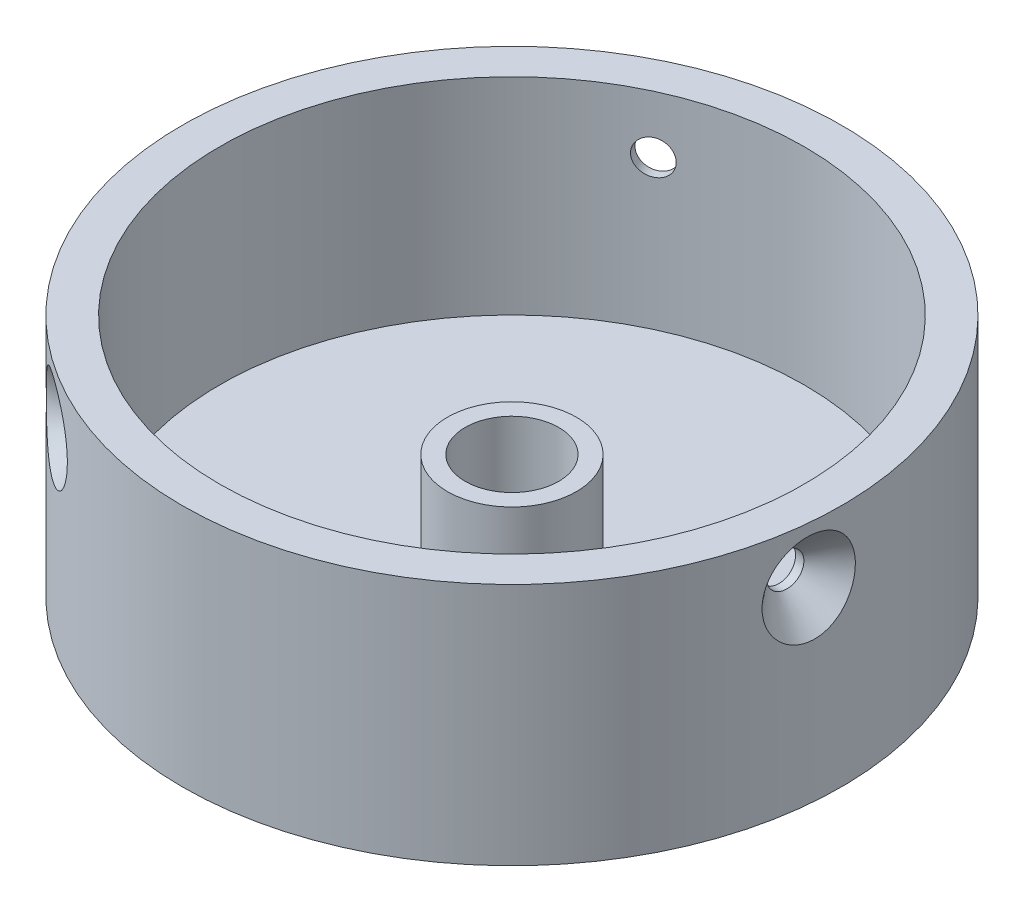
SolidWorks part; units mm, degrees
ref_plane "Front Plane" through (0, 0, 0) normal (0, 0, 1) x (1, 0, 0)
ref_plane "Top Plane" through (0, 0, 0) normal (0, 1, 0) x (1, 0, 0)
ref_plane "Right Plane" through (0, 0, 0) normal (1, 0, 0) x (0, 0, -1)
sketch "Sketch1" plane through (0, 0, 0) normal (0, 1, 0) x (1, 0, 0)
  circle A0 centre (0, 0) radius 23
  dimension "D1" = 46
extrude "Boss-Extrude1" add sketch "Sketch1" along normal blind 17
shell "Shell1" thickness 2.6 removed face at (0, 17, 23)
sketch "Sketch2" plane through (0, 0, 0) normal (0, -1, 0) x (1, 0, 0)
  line L0 (0, -23) -> (0, 5)
  line L1 (6, -18) -> (-6, -18)
  line L2 (-6, -18) -> (-6, 5)
  line L3 (-6, 5) -> (6, 5)
  line L4 (6, -18) -> (6, 5)
  circle A0 centre (0, 0) radius 23 construction
  point P9 (0, -18)
  dimension "D1" = 28
  dimension "D2" = 23
  dimension "D3" = 6
extrude "Boss-Extrude2" add sketch "Sketch2" along normal blind 6 contours L3 L2 L1 L0 | L1 L4 L3 L0 region at (-3, 0, -6.5) region at (3, 0, -6.5)
sketch "Sketch3" plane through (0, 0, -18) normal (0, 0, -1) x (-1, 0, 0)
  line L0 (-6, -3) -> (-4, -3)
  line L2 (-6, -6) -> (-6, 0) construction
  line L3 (-4, -3) -> (-4, 0)
  line L4 (-6, 0) -> (6, 0) construction
  line L5 (-4, 0) -> (-6, 0)
  line L6 (-6, 0) -> (-6, -3)
  line L7 (0, -6) -> (0, 0) construction
  line L8 (-6, -6) -> (6, -6) construction
  line L9 (4, 0) -> (6, 0)
  line L10 (4, -3) -> (4, 0)
  line L11 (6, -3) -> (4, -3)
  line L12 (6, 0) -> (6, -3)
  dimension "D1" = 2
extrude "Cut-Extrude1" cut sketch "Sketch3" against normal through all
sketch "Sketch4" plane through (0, 2.6, 0) normal (0, 1, 0) x (1, 0, 0)
  circle A0 centre (0, 0) radius 4.5
  dimension "D1" = 9
extrude "Boss-Extrude3" add sketch "Sketch4" along normal blind 6
sketch "Sketch5" plane through (0, 8.6, 0) normal (0, 1, 0) x (1, 0, 0)
  circle A0 centre (0, 0) radius 3.265
  dimension "D1" = 6.53
extrude "Cut-Extrude2" cut sketch "Sketch5" against normal blind 13
ref_plane "Plane1" through (0, 0, 5) normal (0, 0, 1) x (1, 0, 0)
sketch "Sketch7" plane through (0, 0, 5) normal (0, 0, 1) x (1, 0, 0)
  line L0 (-1.91, -4.3) -> (-1.91, -1.7)
  line L1 (-1.91, -4.3) -> (1.91, -4.3)
  line L2 (-1.91, -1.7) -> (1.91, -1.7)
  line L3 (1.91, -4.3) -> (1.91, -1.7)
  line L4 (0, -6) -> (0, 0) construction
  line L5 (-1.91, -3) -> (1.91, -3) construction
  line L6 (-6, -6) -> (6, -6) construction
  point P8 (0, -3)
  point P10 (0, -3)
  dimension "D1" = 3.82
  dimension "D2" = 2.6
extrude "Cut-Extrude3" cut sketch "Sketch7" against normal blind 1.71
ref_plane "Plane2" [suppressed] through (0, -3, 0) normal (0, -1, 0) x (-1, 0, 0)
sketch "Sketch8" [suppressed] plane through (0, -3, 0) normal (0, -1, 0) x (-1, 0, 0)
  line L0 (-4, -1.3082) -> (-4, -2.5)
  line L1 (-4, -1.3082) -> (4.0117, -1.3082)
  line L2 (-3.9936, -3.2831) -> (4.0181, -3.2831)
  line L3 (4.0117, -1.3082) -> (4.0117, -2.5)
  line L4 (-4, -5) -> (-4, 18) construction
  line L7 (-3.9936, -3.2831) -> (-4, -2.5)
  line L8 (4.0181, -3.2831) -> (4.0117, -2.5)
extrude "Boss-Extrude4" [suppressed] add sketch "Sketch8" against normal blind 3
hole_wizard "CSK SLOT for M2 Countersunk Flat Head Screw1" positions "3DSketch1" profile "Sketch9" size "M2" standard "ISO" slot yes
sketch3d "3DSketch1"
  line L0 (22.9111, 13, 2.0208) -> (22.9111, 0, 2.0208) construction
  circle A0 centre (0, 0, 0) radius 23 construction
  point P0 (22.9111, 13, 2.0208)
  point P5 (0, 23, 0)
  dimension "D1" = 13
sketch "Sketch9" plane through (22.9111, 13, 2.0208) normal (0, 1, 0) x (0.0879, 0, -0.9961)
  line L0 (0, 0) -> (0, 5.721)
  line L1 (0, 5.721) -> (1.2, 5)
  line L2 (1.2, 5) -> (1.2, 2)
  line L3 (1.2, 2) -> (3.2, 0)
  line L5 (3.2, 0) -> (0, 0)
  line L6 (-1.2, 2) -> (-3.2, 0) construction
  line L10 (0, 5.721) -> (-1.2, 5) construction
  line L11 (0, -6.35) -> (0, 107.95) construction
  dimension "Hole Dia." = 2.4
  dimension "Hole Depth" = 5
  dimension "Near C'Sink Dia." = 6.4
  dimension "Near C'Sink Angle" = 90
  dimension "Drill Angle" = 118
pattern_circular "CirPattern1" count 3 over 360 about axis through (0, 17, 0) along (0, -1, 0) of "CSK SLOT for M2 Countersunk Flat Head Screw1" reverse direction yes
sketch "Sketch10" plane through (0, 0, 3.29) normal (0, 0, 1) x (1, 0, 0)
  line L0 (-1.91, -3) -> (-1.55, -3) construction
  line L1 (-1.91, -1.7) -> (-1.91, -4.3) construction
  line L2 (1.91, -4.3) -> (1.91, -1.7) construction
  line L4 (1.55, -3.9) -> (-1.55, -3.9)
  line L5 (1.55, -3.9) -> (1.55, -1.7)
  line L6 (1.55, -1.7) -> (-1.55, -1.7)
  line L7 (-1.55, -3.9) -> (-1.55, -1.7)
  line L8 (1.91, -1.7) -> (-1.91, -1.7) construction
  line L11 (1.55, -3) -> (1.91, -3) construction
  point P6 (0, -3)
  point P7 (0, -3)
  dimension "D1" = 3.1
extrude "Cut-Extrude4" cut sketch "Sketch10" against normal blind 3
sketch "Sketch11" plane through (0, -3.9, 0) normal (0, 1, 0) x (1, 0, 0)
  line L0 (1.55, -3.29) -> (-1.55, -3.29)
  line L1 (1.55, -3.29) -> (1.55, -2.102)
  line L2 (-1.55, -3.29) -> (-1.55, -2.102)
  line L3 (1.55, -2.102) -> (-1.55, -2.102)
extrude "Boss-Extrude6" add sketch "Sketch11" against normal up to next
fillet "Fillet1" radius 2 3 edges at (-6, -4.5, 5) (0, -6, 5) (6, -4.5, 5)
